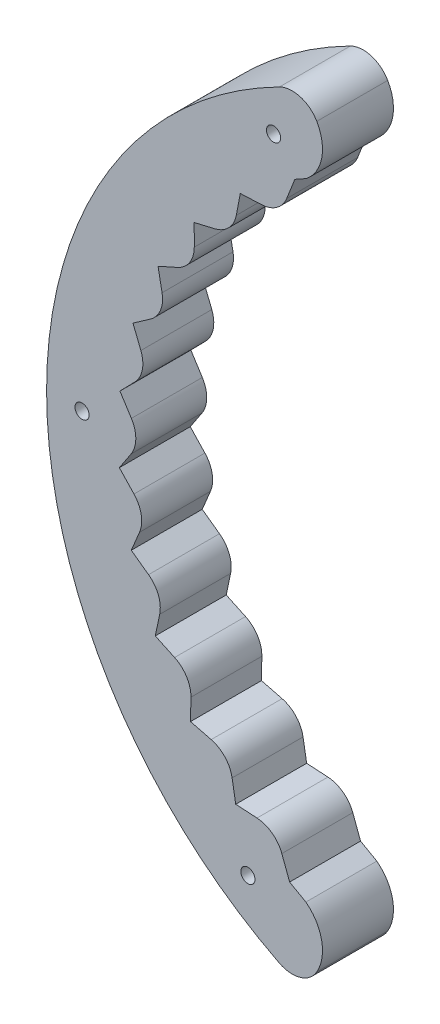
SolidWorks part; units mm, degrees
material "3003 Alaşım"
ref_plane "前视基准面" through (0, 0, 0) normal (0, 0, 1) x (1, 0, 0)
ref_plane "上视基准面" through (0, 0, 0) normal (0, 1, 0) x (1, 0, 0)
ref_plane "右视基准面" through (0, 0, 0) normal (1, 0, 0) x (0, 0, -1)
sketch "草图1" plane through (0, 0, 0) normal (0, 0, 1) x (1, 0, 0)
  line L0 (-50, 0) -> (-25, 0) construction
  line L1 (-25, 74.7114) -> (-25, -53.9079) construction
  line L2 (-23.4461, -44.162) -> (-25.7378, -42.8669)
  line L3 (-25, 43.3013) -> (-26.1465, 40.3921)
  line L10 (-32.6937, 37.73) -> (-33.2521, 34.7773)
  line L11 (-32.6937, 37.73) -> (-29.6915, 37.8626)
  line L12 (-39.1845, 30.9355) -> (-36.2603, 31.6283)
  line L13 (-39.1845, 30.9355) -> (-39.1797, 27.9304)
  line L14 (-44.2872, 23.0451) -> (-41.5446, 24.2736)
  line L15 (-44.2872, 23.0451) -> (-43.7194, 20.0942)
  line L16 (-47.8209, 14.3384) -> (-45.3571, 16.059)
  line L17 (-47.8209, 14.3384) -> (-46.7103, 11.546)
  line L18 (-49.6606, 5.1236) -> (-47.5629, 7.2754)
  line L19 (-49.6606, 5.1236) -> (-48.0464, 2.5889)
  line L20 (-49.7411, -4.2726) -> (-48.0837, -1.7658)
  line L21 (-49.7411, -4.2726) -> (-47.6805, -6.46)
  line L22 (-48.0594, -13.5175) -> (-46.9011, -10.7445)
  line L23 (-48.0594, -13.5175) -> (-45.6255, -15.28)
  line L24 (-44.6753, -22.2835) -> (-44.057, -19.3426)
  line L25 (-44.6753, -22.2835) -> (-41.9541, -23.5587)
  line L26 (-39.7084, -30.2601) -> (-39.6522, -27.2555)
  line L27 (-39.7084, -30.2601) -> (-36.7965, -31.0028)
  line L28 (-33.3349, -37.1647) -> (-33.8427, -34.2028)
  line L29 (-33.3349, -37.1647) -> (-30.3354, -37.3487)
  line L30 (-25.7378, -42.8669) -> (-26.8343, -39.9385)
  line L32 (-27.1796, -53.4909) -> (-27.1875, -53.4868)
  line L33 (-15, -47.697) -> (-15, -66.5436) construction
  line L35 (-25, -54.5436) -> (-25, -66.5436) construction
  arc A0 (-27.1796, 53.4909) -> (-27.1875, -53.4868) centre (0, 0) ccw
  arc A3 (-23.4461, 44.162) -> (-21.9062, 51.9296) centre (-27.0983, 48.9224) ccw
  arc A4 (-26.1465, 40.3921) -> (-29.6915, 37.8626) centre (-29.8679, 41.8587) cw
  arc A5 (-33.2521, 34.7773) -> (-36.2603, 31.6283) centre (-37.1824, 35.5206) cw
  arc A6 (-39.1797, 27.9304) -> (-41.5446, 24.2736) centre (-43.1797, 27.9241) cw
  arc A7 (-43.7194, 20.0942) -> (-45.3571, 16.059) centre (-47.6474, 19.3384) cw
  arc A8 (-46.7103, 11.546) -> (-47.5629, 7.2754) centre (-50.4271, 10.0677) cw
  arc A9 (-48.0464, 2.5889) -> (-48.0837, -1.7658) centre (-51.4203, 0.4403) cw
  arc A10 (-47.6805, -6.46) -> (-46.9011, -10.7445) centre (-50.592, -9.2028) cw
  arc A11 (-45.6255, -15.28) -> (-44.057, -19.3426) centre (-47.9715, -18.5198) cw
  arc A12 (-41.9541, -23.5587) -> (-39.6522, -27.2555) centre (-43.6515, -27.1807) cw
  arc A13 (-36.7965, -31.0028) -> (-33.8427, -34.2028) centre (-37.7852, -34.8787) cw
  arc A14 (-30.3354, -37.3487) -> (-26.8343, -39.9385) centre (-30.5803, -41.3412) cw
  arc A15 (-23.4461, 44.162) -> (-25, 43.3013) centre (0, 0) ccw
  arc A16 (-20.8333, 45.453) -> (-15, -47.697) centre (0, 0) ccw construction
  arc A19 (-25, 54.5436) -> (-25, -54.5436) centre (0, 0) ccw construction
  arc A21 (-27.1796, 53.4909) -> (-21.9062, 51.9296) centre (-25.3676, 49.9248) cw
  circle A26 centre (-31.6201, -45.0019) radius 1
  circle A27 centre (-55, 0) radius 1
  circle A28 centre (-28.0006, 47.3388) radius 1
  arc A30 (-23.4461, -44.162) -> (-21.9062, -51.9296) centre (-27.0983, -48.9224) cw
  arc A31 (-27.1796, -53.4909) -> (-21.9062, -51.9296) centre (-25.3676, -49.9248) ccw
  point P9 (-25, 0)
  point P69 (0, 0)
  dimension "D1" = 60
  dimension "D2" = 10
  dimension "D4" = 4
  dimension "D8" = 4
  dimension "D3" = 25
  dimension "D5" = 11
extrude "凸台1" add sketch "草图1" along normal blind 1
extrude "凸台-拉伸1" add sketch "草图1<2>" along normal blind 8
sketch "草图1<2>" plane through (0, 0, 0) normal (0, 0, 1) x (1, 0, 0) same geometry as "草图1"
extrude "凸台-拉伸2" add sketch "草图1<3>" along normal blind 10
sketch "草图1<3>" plane through (0, 0, 0) normal (0, 0, 1) x (1, 0, 0) same geometry as "草图1"
scale "缩放比例4" scale about centroid uniform scaling yes scale factor 1.5
